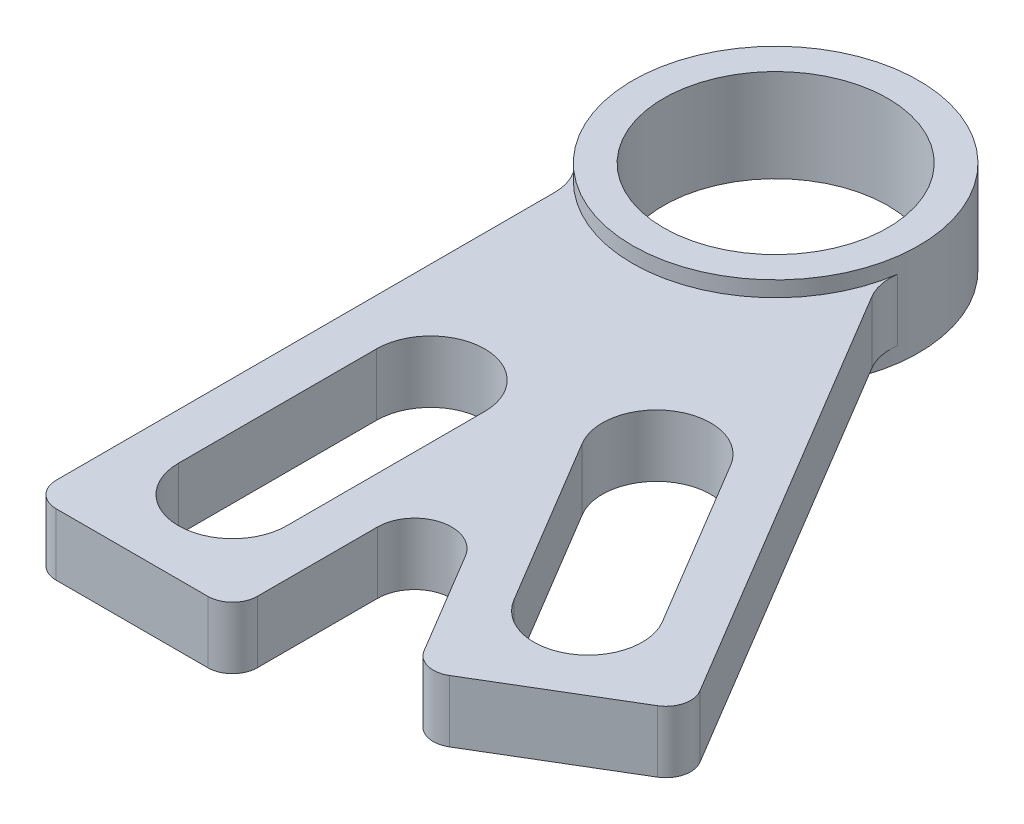
SolidWorks part; units mm, degrees
material "AISI 4130 Steel, normalized at 870C"
ref_plane "Front Plane" through (0, 0, 0) normal (0, 0, 1) x (1, 0, 0)
ref_plane "Top Plane" through (0, 0, 0) normal (0, 1, 0) x (1, 0, 0)
ref_plane "Right Plane" through (0, 0, 0) normal (1, 0, 0) x (0, 0, -1)
sketch "Sketch1" plane through (0, 0, 0) normal (0, 1, 0) x (1, 0, 0)
  line L0 (0, 0) -> (0, -66.04) construction
  line L1 (0, 0) -> (33.8815, -56.6862) construction
  line L2 (0, -55.7213) -> (0, -35.4013) construction
  line L3 (-5.5562, -55.7213) -> (-5.5562, -35.4013)
  line L4 (5.5563, -55.7213) -> (5.5563, -35.4013)
  line L5 (28.5875, -47.829) -> (18.1624, -30.3871) construction
  line L6 (23.8182, -50.6796) -> (13.3931, -33.2377)
  line L7 (33.3568, -44.9784) -> (22.9317, -27.5365)
  line L8 (0, -66.04) -> (0, -61.2775) construction
  line L9 (33.8815, -56.6862) -> (31.4381, -52.5983) construction
  line L10 (-10.3187, -66.04) -> (10.3188, -66.04)
  line L11 (25.0242, -61.9802) -> (42.7387, -51.3923)
  line L12 (-10.3187, -66.04) -> (-10.3187, -10.4432)
  line L13 (10.3188, -66.04) -> (10.3188, -37.3768)
  line L14 (42.7387, -51.3923) -> (14.2151, -3.6701)
  line L15 (25.0242, -61.9802) -> (10.3188, -37.3768)
  line L17 (188.8389, -315.9417) -> (17.7009, -29.6149) construction
  line L22 (0, 0) -> (10.3188, -37.3768) construction
  circle A0 centre (0, 0) radius 11.5062
  circle A1 centre (0, 0) radius 14.6812
  arc A2 (-5.5562, -55.7213) -> (5.5563, -55.7213) centre (0, -55.7213) ccw
  arc A3 (5.5563, -35.4013) -> (-5.5562, -35.4013) centre (0, -35.4013) ccw
  arc A4 (23.8182, -50.6796) -> (33.3568, -44.9784) centre (28.5875, -47.829) ccw
  arc A5 (22.9317, -27.5365) -> (13.3931, -33.2377) centre (18.1624, -30.3871) ccw
  point P8 (0, -45.5613)
  point P13 (23.3749, -39.108)
  point P25 (0, -66.04)
  point P27 (33.8815, -56.6862)
  dimension "D2" = 29.3624
  dimension "D3" = 4.7625
  dimension "D4" = 4.7625
  dimension "D5" = 20.32
  dimension "D6" = 66.04
  dimension "D7" = 20.6375
extrude "Bearing_Insert_Extrude" add sketch "Sketch1" along normal mid plane 9.525 contours A1 A0 region at (-5.4988, 0, -13.1636)
extrude "Apex_Slot_Insert_Extrude" add sketch "Sketch1<4>" along normal mid plane 6.35 contours A1 L12 L10 L13 L15 L11 L14 A5 L7 A4 L6 A3 L4 A2 L3 | L13 L15 region at (9.9891, 0, 36.1827)
sketch "Sketch1<4>" plane through (0, 0, 0) normal (0, 1, 0) x (1, 0, 0) same geometry as "Sketch1"
fillet "Fillet1" radius 5.08 2 edges at (14.2151, 0, 3.6701) (-10.3187, 0, 10.4432)
fillet "Fillet2" radius 2.54 4 edges at (42.7387, 0, 51.3923) (25.0242, 0, 61.9802) (10.3188, 0, 66.04) (-10.3187, 0, 66.04)
fillet "Fillet3" radius 3.81 1 edges at (10.3188, 0, 37.3768)
equation "\"Apex_thickness\"= .25"
equation "\"Bearing_diameter\"= 0.906in"
equation "\"A-arm_angle\"= 39.1893"
equation "\"D1@Sketch1\"=\"Bearing_diameter\""
equation "\"D1@Apex_Slot_Insert_Extrude\"=\"Apex_thickness\""
